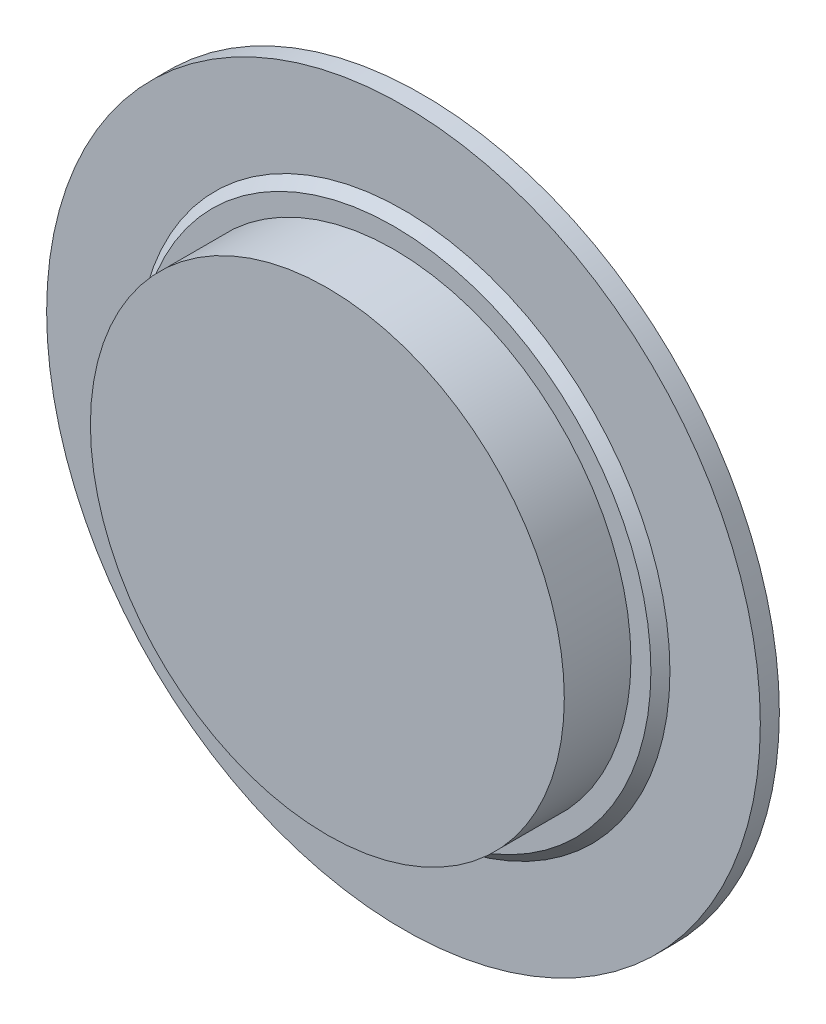
SolidWorks part; units mm, degrees
ref_plane "Front Plane" through (0, 0, 0) normal (0, 0, 1) x (1, 0, 0)
ref_plane "Top Plane" through (0, 0, 0) normal (0, 1, 0) x (1, 0, 0)
ref_plane "Right Plane" through (0, 0, 0) normal (1, 0, 0) x (0, 0, -1)
sketch "Sketch1" plane through (0, 0, 0) normal (0, 0, 1) x (1, 0, 0)
  circle A0 centre (0, 0) radius 37.5
  dimension "D1" = 75
extrude "Boss-Extrude1" add sketch "Sketch1" along normal blind 2
sketch "Sketch5" plane through (0, 0, 2) normal (0, 0, 1) x (1, 0, 0)
  circle A0 centre (0, 0) radius 28
  dimension "D1" = 56
extrude "Boss-Extrude5" add sketch "Sketch5" along normal blind 1
sketch "Sketch2" plane through (0, 0, 3) normal (0, 0, 1) x (1, 0, 0)
  circle A0 centre (0, 0) radius 24.9
  dimension "D1" = 49.8
extrude "Boss-Extrude2" add sketch "Sketch2" along normal blind 7
chamfer "Chamfer1" distance 1 distance2 1 1 edges at (28, 0, 3)
